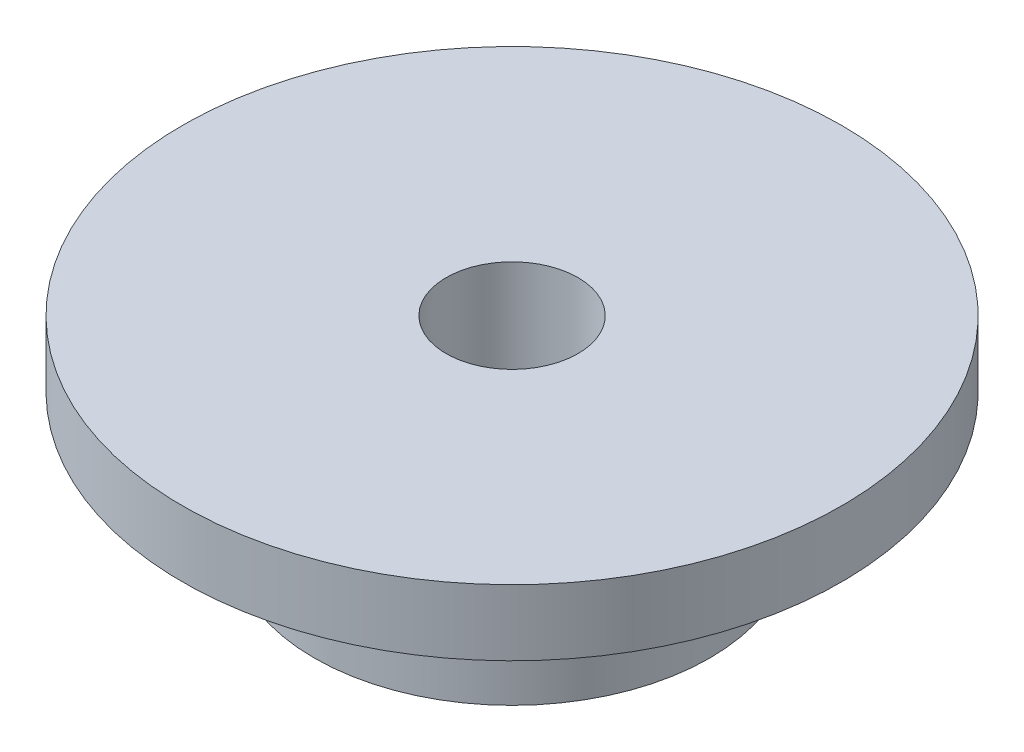
SolidWorks part; units mm, degrees
material "Сталь ШХ15 ГОСТ 801-78"
ref_plane "Plane1" through (0, 0, 0) normal (0, 0, 1) x (1, 0, 0)
ref_plane "Plane2" through (0, 0, 0) normal (0, 1, 0) x (1, 0, 0)
ref_plane "Plane3" through (0, 0, 0) normal (1, 0, 0) x (0, 0, -1)
sketch "Эскиз1" plane through (0, 0, 0) normal (0, 0, 1) x (1, 0, 0)
  line L6 (0, 0) -> (0, 6.4893) construction
  line L7 (2, -0.354) -> (2, 5.646)
  line L8 (2, 5.646) -> (10, 5.646)
  line L9 (10, 5.646) -> (10, 3.646)
  line L10 (10, 3.646) -> (6, 3.646)
  line L11 (6, 3.646) -> (6, -0.354)
  line L12 (6, -0.354) -> (2, -0.354)
  dimension "D1" = 2
  dimension "D2" = 6
  dimension "D3" = 10
  dimension "D4" = 2
  dimension "D5" = 6
revolve "Повернуть1" add sketch "Эскиз1" angle 360 about L6
